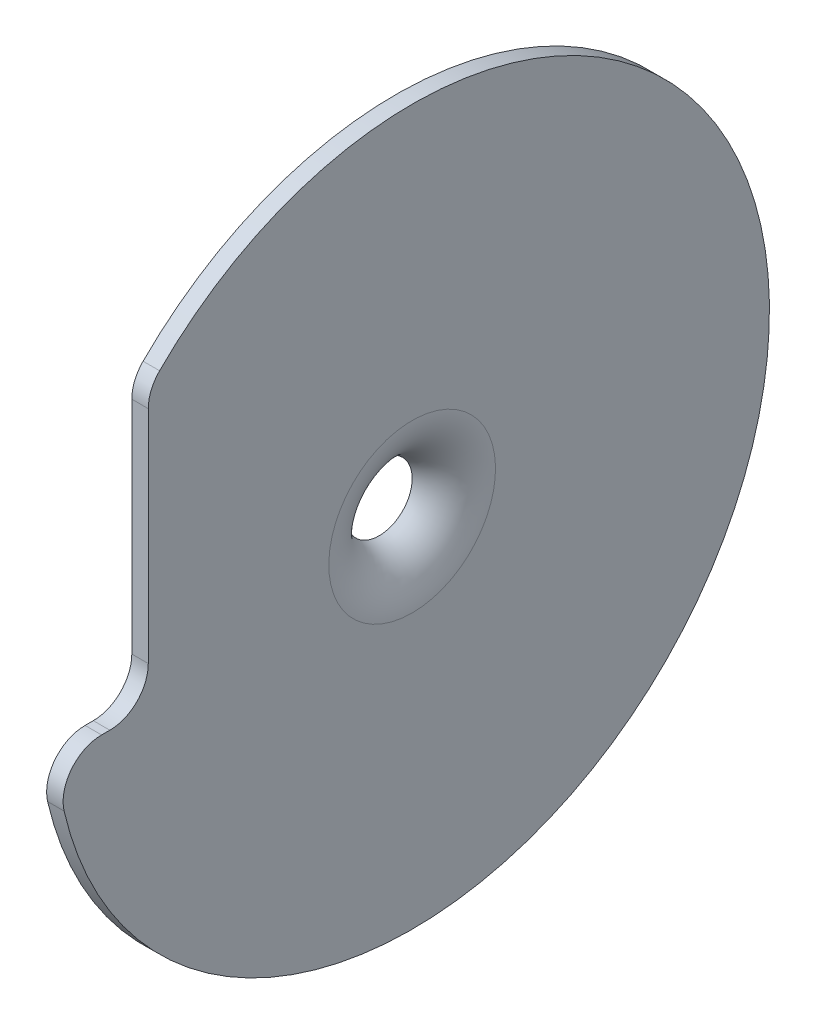
SolidWorks part; units mm, degrees
material "ABS"
ref_plane "Front Plane" through (0, 0, 0) normal (0, 0, 1) x (1, 0, 0)
ref_plane "Top Plane" through (0, 0, 0) normal (0, 1, 0) x (1, 0, 0)
ref_plane "Right Plane" through (0, 0, 0) normal (1, 0, 0) x (0, 0, -1)
sketch "Sketch1" plane through (-19, 0, 0) normal (-1, 0, 0) x (0, 0, 1)
  line L0 (-2, 25.5) -> (-2, -62.2019)
  line L1 (-2, -24.5) -> (14.7106, -24.5)
  circle A0 centre (-50, -18.3727) radius 65
  arc A1 (-50, -83.1319) -> (-50, 46.3864) centre (-50, -18.3727) ccw construction
  line M1 (-83, 19) -> (-83, -19)
  line M2 (-83, -19) -> (-31, -19)
  line M3 (-31, -19) -> (-31, 19)
  line M4 (-31, 19) -> (-83, 19)
  dimension "D1" = 130
  dimension "D2" = 50
extrude "BULK EXTRUDE" add sketch "Sketch1" along normal blind 3 contours L0 A0 M1 M4 M3 M2 | M4 M1 M2 M3 | L0 A0 L1 region at (-19, -38.6211, 4.4839) region at (-19, -21.9062, -54.1169) region at (-19, 0, -57)
fillet "Fillet1" radius 7 3 edges at (-20.5, 25.4565, -2) (-20.5, -24.5, 14.7106) (-20.5, -24.5, -2)
sketch "Sketch2" plane through (-22, 0, 0) normal (-1, 0, 0) x (0, 0, 1)
  circle A0 centre (-50, -18.3727) radius 31.5
  arc A1 (-4.0517, 27.6029) -> (13.3133, -33.0843) centre (-50, -18.3727) ccw construction
  dimension "D1" = 63
extrude "MOTOR SUPPORT" add sketch "Sketch2" along normal blind 3
sketch "Sketch3" plane through (-25, 0, 0) normal (-1, 0, 0) x (0, 0, 1)
  circle A0 centre (-50, -18.3727) radius 6
  circle A1 centre (-50, -18.3727) radius 31.5 construction
  dimension "D1" = 12
extrude "WIRE PASSTHRU" cut sketch "Sketch3" against normal through all
fillet "Fillet2" radius 10 1 edges at (-19, -24.3727, -50)
